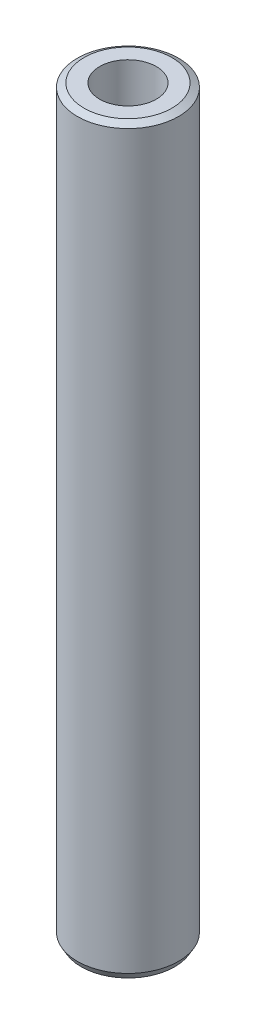
SolidWorks part; units mm, degrees
ref_plane "Front Plane" through (0, 0, 0) normal (0, 0, 1) x (1, 0, 0)
ref_plane "Top Plane" through (0, 0, 0) normal (0, 1, 0) x (1, 0, 0)
ref_plane "Right Plane" through (0, 0, 0) normal (1, 0, 0) x (0, 0, -1)
sketch "Sketch1" plane through (0, 0, 0) normal (0, 1, 0) x (1, 0, 0)
  circle A0 centre (0, 0) radius 27.5
  dimension "SHAFT_OD" = 55
extrude "Boss-Extrude1" add sketch "Sketch1" along normal blind 403.4329
sketch "Sketch2" plane through (0, 0, 0) normal (0, 1, 0) x (1, 0, 0)
  circle A0 centre (0, 0) radius 15.409
  dimension "BORE_D" = 30.8179
extrude "Cut-Extrude1" cut sketch "Sketch2" along normal through all
chamfer "Chamfer1" distance 2.0919 angle 60 2 edges at (0, 403.4329, 27.5) (0, 0, 27.5) first distance on face at (0, 403.4329, 27.5) first distance on face at (0, 0, 15.409)
